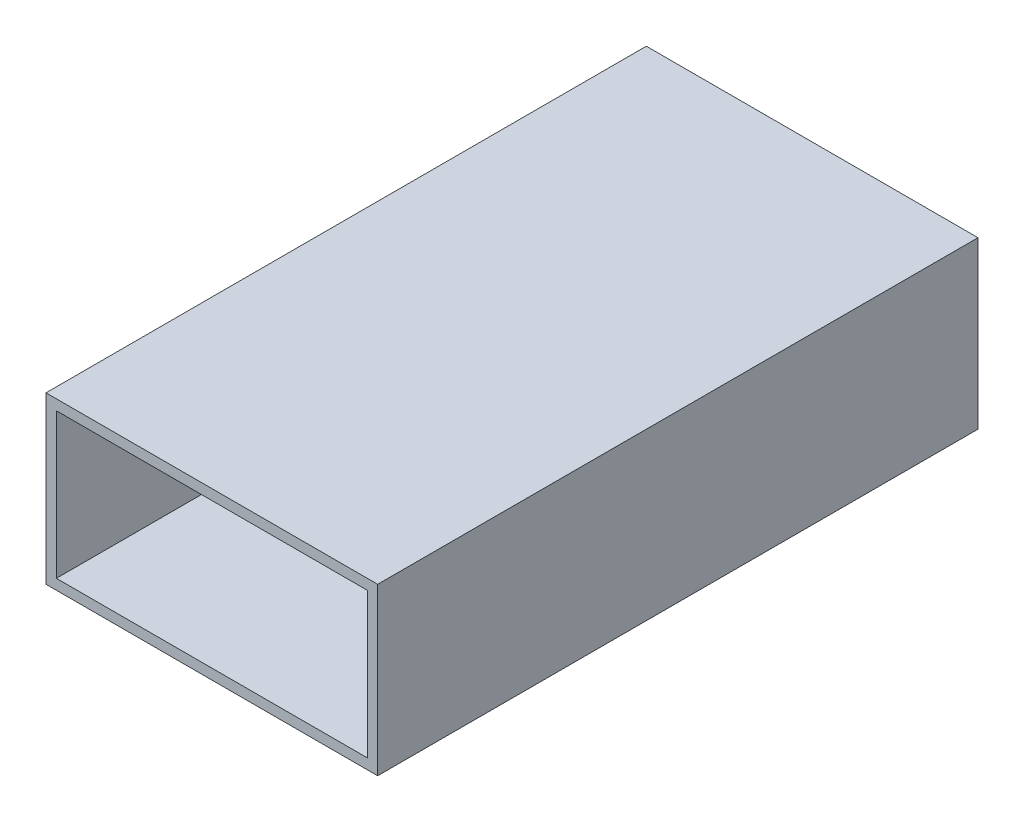
SolidWorks part; units mm, degrees
material "6061-T6 (SS)"
ref_plane "Front Plane" through (0, 0, 0) normal (0, 0, 1) x (1, 0, 0)
ref_plane "Top Plane" through (0, 0, 0) normal (0, 1, 0) x (1, 0, 0)
ref_plane "Right Plane" through (0, 0, 0) normal (1, 0, 0) x (0, 0, -1)
sketch "Sketch1" plane through (0, 0, 0) normal (0, 0, 1) x (1, 0, 0)
  line L1 (-25.4, -12.7) -> (25.4, -12.7)
  line L2 (-25.4, -12.7) -> (-25.4, 12.7)
  line L3 (-25.4, 12.7) -> (25.4, 12.7)
  line L4 (25.4, -12.7) -> (25.4, 12.7)
  line L5 (-25.4, -12.7) -> (25.4, 12.7) construction
  line L6 (-25.4, 12.7) -> (25.4, -12.7) construction
  line L7 (-23.8125, -11.1125) -> (23.8125, -11.1125)
  line L8 (-23.8125, -11.1125) -> (-23.8125, 11.1125)
  line L9 (-23.8125, 11.1125) -> (23.8125, 11.1125)
  line L10 (23.8125, -11.1125) -> (23.8125, 11.1125)
  line L11 (-23.8125, -11.1125) -> (23.8125, 11.1125) construction
  line L12 (-23.8125, 11.1125) -> (23.8125, -11.1125) construction
  point P0 (0, 0)
  point P6 (0, 0)
  dimension "D1" = 50.8
  dimension "D2" = 25.4
  dimension "D3" = 1.5875
  dimension "D4" = 1.5875
extrude "Boss-Extrude1" add sketch "Sketch1" along normal mid plane 91.948
